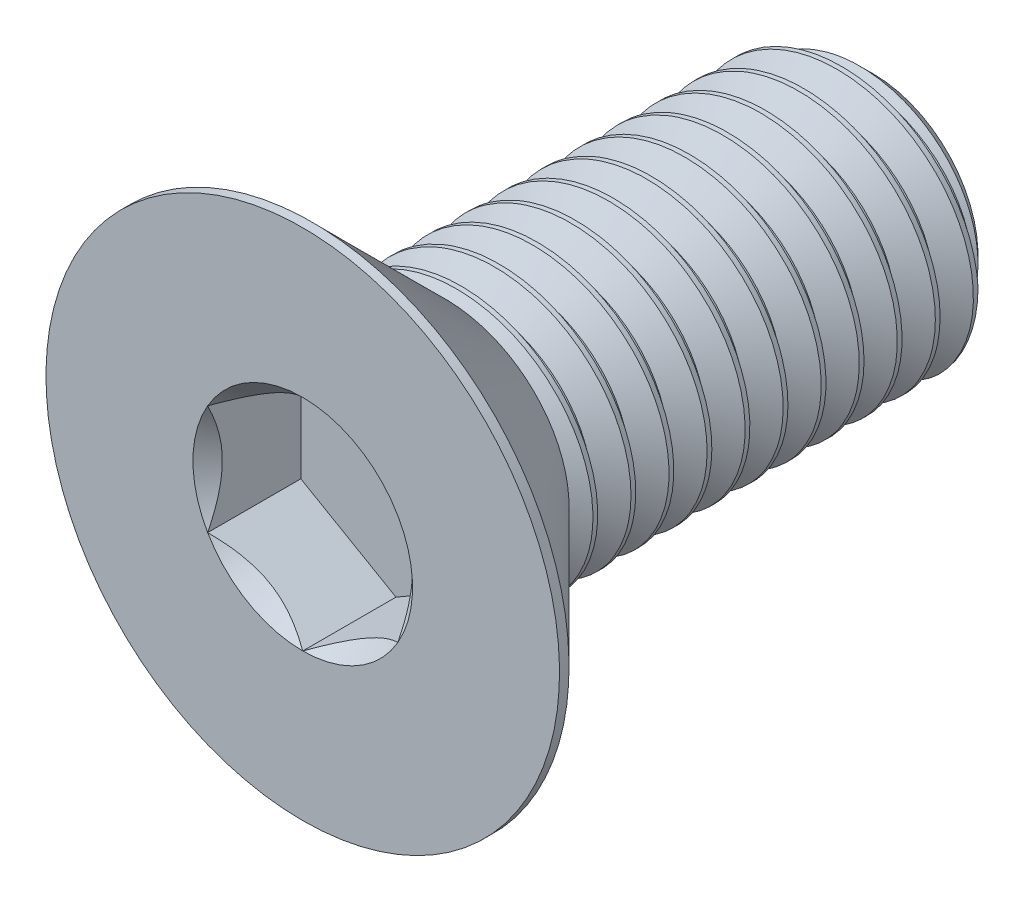
SolidWorks part; units mm, degrees
ref_plane "Front" through (0, 0, 0) normal (0, 0, 1) x (1, 0, 0)
ref_plane "Top" through (0, 0, 0) normal (0, 1, 0) x (1, 0, 0)
ref_plane "Right" through (0, 0, 0) normal (1, 0, 0) x (0, 0, -1)
sketch "Sketch1" plane through (0, 0, 0) normal (1, 0, 0) x (0, 0, -1)
  line L0 (0, 13.5) -> (0.5, 13.5) construction
  line L1 (0.5, 13.5) -> (7, 7) construction
  line L2 (0, 7) -> (30, 7)
  line L3 (30, 7) -> (30, 0)
  line L4 (30, 0) -> (0, 0)
  line L5 (0, 0) -> (0, 13.5) construction
  line L6 (0, 13.5) -> (0, -13.5) construction
  line L7 (30, 7) -> (30, -7) construction
  line L8 (0, -13.5) -> (0.5, -13.5) construction
  line L9 (0.5, -13.5) -> (7, -7) construction
  line L11 (0, 7) -> (0, 0)
  line L12 (7, 7) -> (7, 0) construction
revolve "Revolve1" add sketch "Sketch1" angle 360 mid plane about L4
sketch "Sketch3" plane through (0, 0, -30) normal (0, 0, -1) x (-1, 0, 0)
  circle A0 centre (0, 0) radius 7
curve "Helix/Spiral1" pitch 2 height 30 radius 7 centre (0, 0, -30) axis (0, 0, 1) start towards (0, 1, 0)
sketch "Sketch2" plane through (0, 0, 0) normal (1, 0, 0) x (0, 0, -1)
  line L0 (30, 7) -> (31.75, 7)
  line L1 (31.75, 7) -> (31, 5.701)
  line L2 (31, 5.701) -> (30.75, 5.701)
  line L3 (30.75, 5.701) -> (30, 7)
  line L4 (30.375, 6.3505) -> (31.375, 6.3505) construction
  dimension "D1" = 60
  dimension "D2" = 0.25
  dimension "D3" = 1
chamfer "Chamfer1" distance 1.5 angle 45 1 edges at (0, 7, -30)
sweep "Cut-Sweep1" cut profiles "Sketch2" path "Helix/Spiral1" align with end faces yes
sketch "Sketch7" plane through (0, 0, 0) normal (1, 0, 0) x (0, 0, -1)
  line L0 (0, 13.5) -> (0.5, 13.5) construction
  line L1 (0.5, 13.5) -> (7, 7) construction
  line L2 (0, 13.5) -> (0.5, 13.5)
  line L3 (0.5, 13.5) -> (7, 7)
  line L4 (7, 7) -> (7, 0) construction
  line L5 (7, 7) -> (7, 0)
  line L7 (0, 0) -> (0, 13.5) construction
  line L8 (0, 0) -> (0, 13.5)
  line L9 (0, 0) -> (7, 0)
  line L10 (14.85, 0) -> (-14.85, 0) construction
revolve "Revolve2" add sketch "Sketch7" angle 360 mid plane about L9
ref_plane "Plane1" through (0, 0, -7) normal (0, 0, 1) x (1, 0, 0)
sketch "Sketch8" plane through (0, 0, -7) normal (0, 0, 1) x (1, 0, 0)
  circle A0 centre (0, 0) radius 7
extrude "Boss-Extrude1" add sketch "Sketch8" against normal through all draft 45
sketch "Sketch5" plane through (0, 0, 0) normal (0, 0, 1) x (1, 0, 0)
  line L1 (5, -2.8868) -> (5, 2.8868)
  line L2 (5, 2.8868) -> (0, 5.7735)
  line L3 (0, 5.7735) -> (-5, 2.8868)
  line L4 (-5, 2.8868) -> (-5, -2.8868)
  line L5 (-5, -2.8868) -> (0, -5.7735)
  line L6 (0, -5.7735) -> (5, -2.8868)
  circle A0 centre (0, 0) radius 5 construction
  dimension "Hex" = 10
extrude "Cut-Extrude2" cut sketch "Sketch5" against normal blind 4.9
sketch "Sketch6" plane through (0, 0, 0) normal (0, 0, 1) x (1, 0, 0)
  circle A0 centre (0, 0) radius 5.7735
extrude "Cut-Extrude3" cut sketch "Sketch6" against normal blind 4.9 draft 45
sketch "Sketch9" [suppressed] plane through (0, 0, -1.5) normal (0, 0, 1) x (1, 0, 0)
  circle A1 centre (0, 0) radius 1.25
  circle A2 centre (0, 0) radius 1.25
  point P0 (0, 1.25)
  dimension "D1" = 0
extrude "Boss-Extrude2" [suppressed] add sketch "Sketch9" against normal offset from surface (3.5 mm away) 26 up to face at (0, 5.5, -30)
fillet "Fillet1" [suppressed] radius 1.4
sketch "Sketch10" plane through (0, 0, 0) normal (1, 0, 0) x (0, 0, -1)
  line L0 (30, 7) -> (30, -7) construction
  point P0 (27, -7)
  dimension "D1" = 3
equation "\"D3@Helix/Spiral1\" = \"Lg@Sketch1\""
equation "\"D2@Sketch2\" = \"D4@Helix/Spiral1\" * .125"
equation "\"D3@Sketch2\" = \"D4@Helix/Spiral1\" * .5"
equation "\"D1@Chamfer1\" = \"D4@Helix/Spiral1\" * .75"
equation "\"D1@Cut-Extrude2\" = \"Head Ht@Sketch1\" * .7"
equation "\"D1@Sketch10\" = \"D4@Helix/Spiral1\" * 1.5"
equation "\"D1@Cut-Extrude3\" = \"D1@Cut-Extrude2\""
equation "\"D1@Fillet1\" = \"Dia@Sketch1\" * .1"
